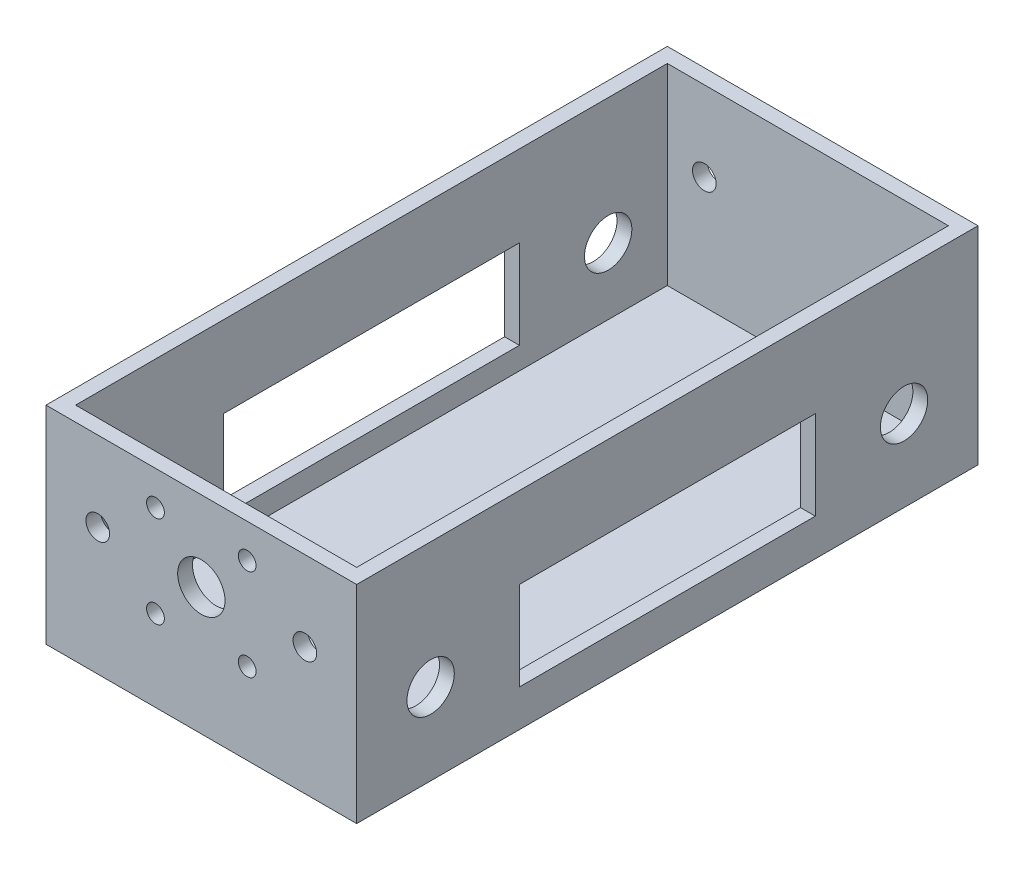
SolidWorks part; units mm, degrees
ref_plane "Front Plane" through (0, 0, 0) normal (0, 0, 1) x (1, 0, 0)
ref_plane "Top Plane" through (0, 0, 0) normal (0, 1, 0) x (1, 0, 0)
ref_plane "Right Plane" through (0, 0, 0) normal (1, 0, 0) x (0, 0, -1)
sketch "Sketch1" plane through (0, 0, 0) normal (0, 1, 0) x (1, 0, 0)
  line L1 (-50, 100) -> (50, 100)
  line L2 (-50, 100) -> (-50, -100)
  line L3 (-50, -100) -> (50, -100)
  line L4 (50, 100) -> (50, -100)
  line L5 (-50, 100) -> (50, -100) construction
  line L6 (-50, -100) -> (50, 100) construction
  point P0 (0, 0)
  dimension "D1" = 200
  dimension "D2" = 100
extrude "Boss-Extrude1" add sketch "Sketch1" along normal mid plane 5
sketch "Sketch2" plane through (-50, 0, 0) normal (-1, 0, 0) x (0, 0, 1)
  line L0 (100, 2.5) -> (100, -2.5) construction
  line L1 (-100, -2.5) -> (100, -2.5)
  line L2 (-100, -2.5) -> (-100, 67.5)
  line L3 (-100, 67.5) -> (100, 67.5)
  line L4 (100, -2.5) -> (100, 67.5)
  dimension "D1" = 70
extrude "Boss-Extrude2" add sketch "Sketch2" along normal mid plane 5
sketch "Sketch3" plane through (-52.5, 0, 0) normal (-1, 0, 0) x (0, 0, 1)
  line L0 (0, -2.5) -> (0, 67.5) construction
  line L1 (-100, -2.5) -> (100, -2.5) construction
  line L2 (100, 67.5) -> (-100, 67.5) construction
  circle A0 centre (-80, 25) radius 8
  circle A1 centre (80, 25) radius 8
  dimension "D3" = 16
  dimension "D1" = 80
  dimension "D2" = 25
extrude "Cut-Extrude1" cut sketch "Sketch3" against normal up to surface (5 mm away) up to face at (-47.5, 35, 0)
mirror "Mirror1" about plane through (0, 0, 0) normal (1, 0, 0) of "Boss-Extrude2", "Cut-Extrude1"
sketch "Sketch4" plane through (0, 0, -100) normal (0, 0, -1) x (-1, 0, 0)
  line L1 (-52.5, 67.5) -> (52.5, 67.5)
  line L2 (-52.5, 67.5) -> (-52.5, -2.5)
  line L3 (-52.5, -2.5) -> (52.5, -2.5)
  line L4 (52.5, 67.5) -> (52.5, -2.5)
extrude "Boss-Extrude3" add sketch "Sketch4" along normal blind 5
sketch "Sketch5" plane through (0, 0, 100) normal (0, 0, 1) x (1, 0, 0)
  line L1 (-52.5, 67.5) -> (52.5, 67.5)
  line L2 (-52.5, 67.5) -> (-52.5, -2.5)
  line L3 (-52.5, -2.5) -> (52.5, -2.5)
  line L4 (52.5, 67.5) -> (52.5, -2.5)
extrude "Boss-Extrude4" add sketch "Sketch5" along normal blind 5
sketch "Sketch6" plane through (-52.5, 0, 0) normal (-1, 0, 0) x (0, 0, 1)
  line L0 (0, 0) -> (0, 10) construction
  line L5 (-50, 40) -> (50, 40)
  line L6 (-50, 40) -> (-50, 10)
  line L7 (-50, 10) -> (50, 10)
  line L8 (50, 40) -> (50, 10)
  dimension "D1" = 10
  dimension "D2" = 30
  dimension "D3" = 100
extrude "Cut-Extrude2" cut sketch "Sketch6" against normal through all
sketch "Sketch7" plane through (0, 0, 105) normal (0, 0, -1) x (-1, 0, 0)
  line L0 (0, 40.5) -> (0, 0) construction
  line L1 (-15.5, 56) -> (15.5, 56) construction
  line L2 (-15.5, 56) -> (-15.5, 25) construction
  line L3 (-15.5, 25) -> (15.5, 25) construction
  line L4 (15.5, 56) -> (15.5, 25) construction
  line L5 (-15.5, 56) -> (15.5, 25) construction
  line L6 (-15.5, 25) -> (15.5, 56) construction
  circle A0 centre (-15.5, 56) radius 3
  circle A1 centre (-15.5, 25) radius 3
  circle A2 centre (15.5, 56) radius 3
  circle A3 centre (15.5, 25) radius 3
  circle A4 centre (0, 40.5) radius 8
  circle A5 centre (-35, 40.5) radius 4
  circle A6 centre (35, 40.5) radius 4
  point P0 (0, 40.5)
  dimension "D4" = 6
  dimension "D5" = 16
  dimension "D6" = 8
  dimension "D1" = 31
  dimension "D2" = 31
  dimension "D3" = 25
  dimension "D7" = 35
extrude "Cut-Extrude5" cut sketch "Sketch7" along normal through all contours A6 | A5 region at (35, 40.5, 105) region at (-35, 40.5, 105)
extrude "Cut-Extrude6" cut sketch "Sketch7<5>" along normal up to surface (5 mm away) contours A2 | A0 | A3 | A1 | A4 region at (15.5, 56, 105) region at (15.5, 25, 105) region at (-15.5, 56, 105) region at (-15.5, 25, 105) region at (0, 40.5, 105) up to face at (0, 35, 100)
sketch "Sketch7<5>" plane through (0, 0, 105) normal (0, 0, -1) x (-1, 0, 0) same geometry as "Sketch7"
